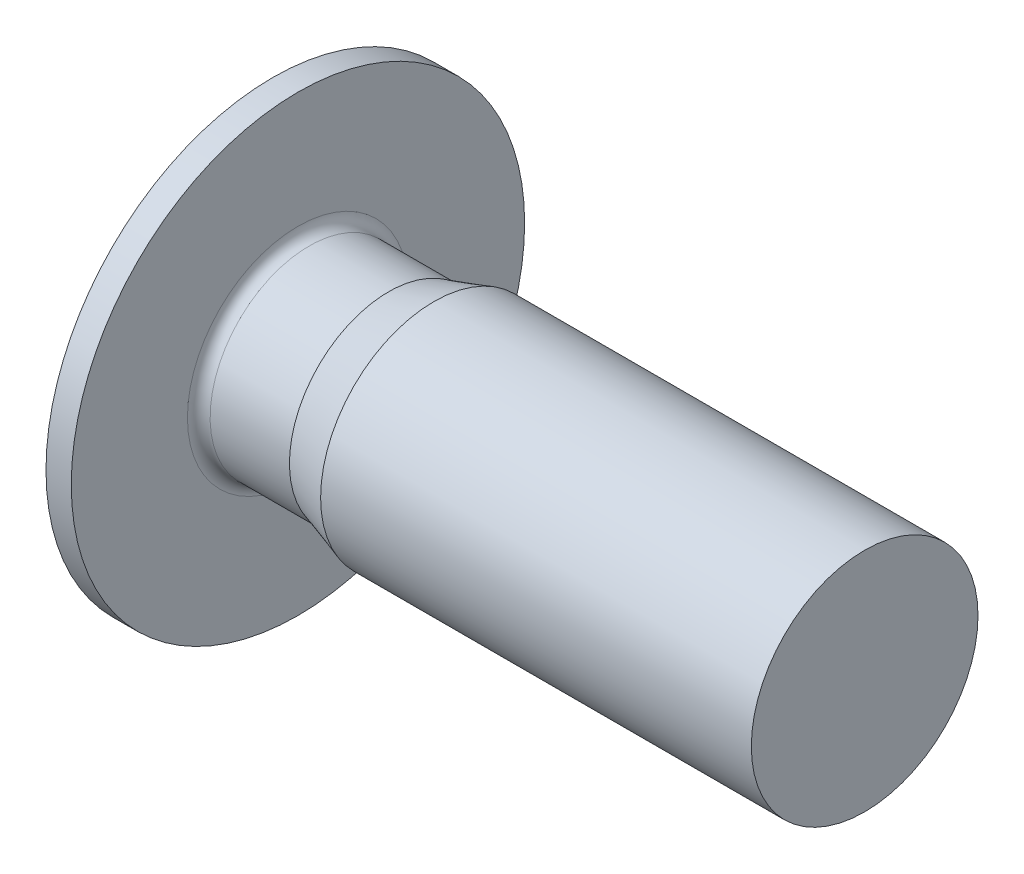
SolidWorks part; units mm, degrees
material "SCM435"
ref_plane "Front Plane" through (0, 0, 0) normal (0, 0, 1) x (1, 0, 0)
ref_plane "Top Plane" through (0, 0, 0) normal (0, 1, 0) x (1, 0, 0)
ref_plane "Right Plane" through (0, 0, 0) normal (1, 0, 0) x (0, 0, -1)
sketch "Sketch1" plane through (0, 0, 0) normal (0, 0, 1) x (1, 0, 0)
  line L0 (-0.5, 0) -> (5, 0) construction
  line L1 (-0.5, 0) -> (-0.5, 1.52)
  line L2 (-0.2229, 2) -> (0, 2)
  line L3 (0, 2) -> (0, 0.875)
  line L4 (1.2, 1) -> (5, 1)
  line L5 (5, 1) -> (5, 0)
  line L6 (5, 0) -> (-0.5, 0)
  line L7 (1.2, 1) -> (0.8, 0.875)
  line L8 (0.8, 0.875) -> (0, 0.875)
  line L9 (-0.2229, 2) -> (-0.5, 1.52)
  line L10 (-0.5, 0) -> (5, 0) construction
  dimension "A" = 4
  dimension "M" = 2
  dimension "L" = 5
  dimension "MSM_1" = 3.04
  dimension "E_s" = 1.2
  dimension "E" = 0.5
  dimension "FIX_1" = 30
  dimension "MSM_2" = 1.75
  dimension "MSM_3" = 0.4
revolve "Revolve1" add sketch "Sketch1" angle 360 about L0
cosmetic thread "Thread1" parameters "ATL_1"=3.8, "ATD"=1.567
fillet "Fillet1" radius 0.1 1 edges at (0, -0.875, 0)
sketch "Sketch2" plane through (-0.5, 0, 0) normal (-1, 0, 0) x (0, 0, 1)
  line L1 (0, 0.7506) -> (-0.65, 0.3753)
  line L2 (-0.65, 0.3753) -> (-0.65, -0.3753)
  line L3 (-0.65, -0.3753) -> (0, -0.7506)
  line L4 (0, -0.7506) -> (0.65, -0.3753)
  line L5 (0.65, -0.3753) -> (0.65, 0.3753)
  line L6 (0.65, 0.3753) -> (0, 0.7506)
  circle A0 centre (0, 0) radius 0.65 construction
  dimension "B" = 1.3
extrude "Cut-Extrude1" cut sketch "Sketch2" against normal blind 1.2
sketch "Sketch3" plane through (0, 0, 0) normal (0, 0, 1) x (1, 0, 0)
  line L0 (0.7, 0) -> (1.0906, 0) construction
  line L1 (0.7, 0) -> (0.7, 0.65)
  line L2 (0.7, 0.65) -> (1.0906, 0)
  line L3 (1.0906, 0) -> (0.7, 0)
  line L5 (0.7, 0.3753) -> (0.7, -0.3753) construction
  dimension "FIX_3" = 59
  dimension "B" = 1.3
revolve "Cut-Revolve1" cut sketch "Sketch3" angle 360 about L0
equation "\"ATL_1@Thread1\" = \"L@Sketch1\" - \"E_s@Sketch1\""
